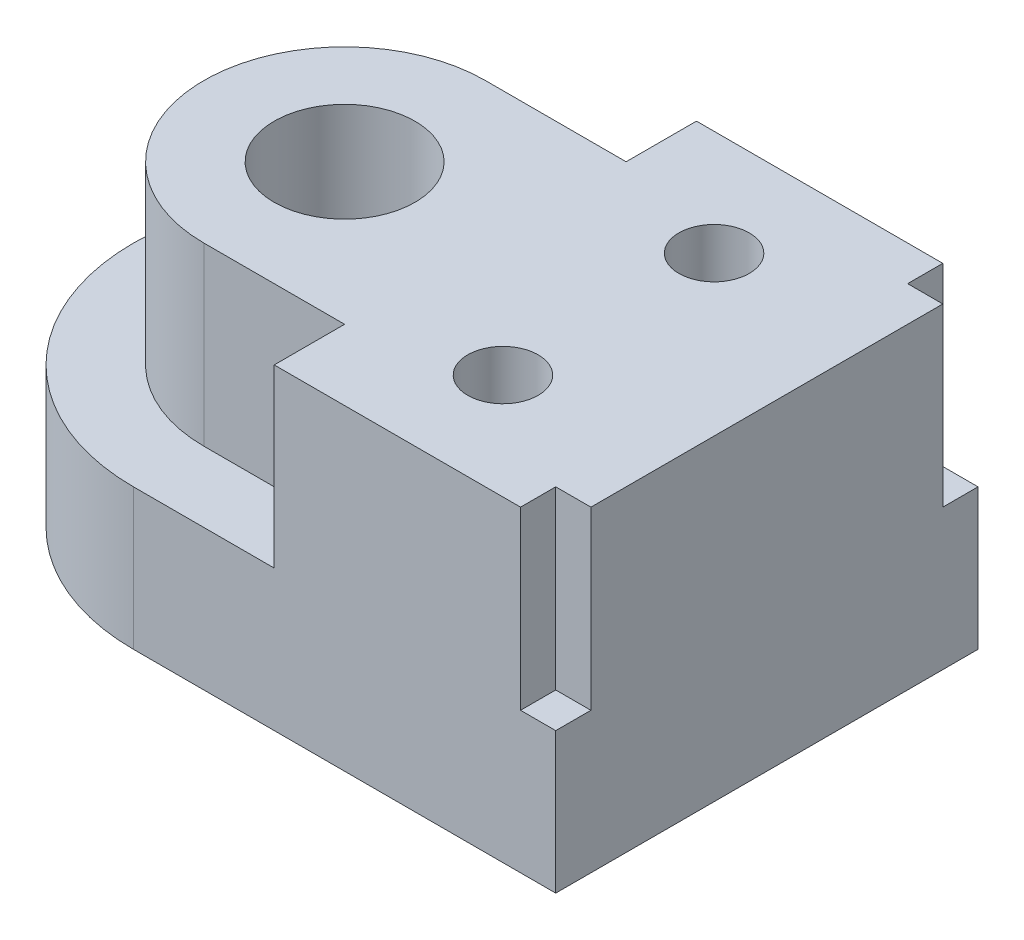
SolidWorks part; units mm, degrees
ref_plane "Front Plane" through (0, 0, 0) normal (0, 0, 1) x (1, 0, 0)
ref_plane "Top Plane" through (0, 0, 0) normal (0, 1, 0) x (1, 0, 0)
ref_plane "Right Plane" through (0, 0, 0) normal (1, 0, 0) x (0, 0, -1)
sketch "Sketch1" plane through (0, 0, 0) normal (0, 1, 0) x (1, 0, 0)
  line L0 (0, 30) -> (60, 30)
  line L1 (60, 30) -> (60, -30)
  line L2 (60, -30) -> (0, -30)
  line L3 (-20, 0) -> (60, 0) construction
  line L4 (0, 20) -> (20, 20)
  line L5 (20, 20) -> (20, 30)
  line L6 (20, -20) -> (20, -30)
  line L7 (0, -20) -> (20, -20)
  arc A0 (0, 30) -> (0, -30) centre (0, 0) ccw
  circle A1 centre (0, 0) radius 20
  dimension "D1" = 60
  dimension "D3" = 40
  dimension "D2" = 60
extrude "Boss-Extrude2" add sketch "Sketch1" along normal blind 45 contours L3 A1 | L3 A1 L7 L6 L2 L1 | A1 L3 L1 L0 L5 L4 | A1 L3 region at (38.3666, 0, -15.0356) region at (38.3666, 0, 15.0356) region at (0, 0, -8.4883) region at (0, 0, 8.4883)
extrude "Boss-Extrude3" add sketch "Sketch1<3>" along normal blind 20 contours A1 L4 L5 L0 A0 L2 L6 L7 region at (10, 0, -29.219)
sketch "Sketch1<3>" plane through (0, 0, 0) normal (0, 1, 0) x (1, 0, 0) same geometry as "Sketch1"
sketch "Sketch3" plane through (0, 45, 0) normal (0, 1, 0) x (1, 0, 0)
  line L0 (55, -30) -> (55, -25)
  line L1 (55, -25) -> (60, -25)
  line L2 (55, 30) -> (55, 25)
  line L3 (55, 25) -> (60, 25)
  line L4 (60, 25) -> (60, 30)
  line L7 (20, 20) -> (0, 20)
  line L8 (0, -20) -> (20, -20)
  line L9 (20, -20) -> (20, -30)
  line L10 (20, -30) -> (60, -30)
  line L11 (60, -30) -> (60, 30)
  line L12 (60, 30) -> (20, 30)
  line L13 (20, 30) -> (20, 20)
  line L17 (55, -30) -> (60, -30)
  line L18 (60, -30) -> (60, -25)
  line L19 (60, 30) -> (55, 30)
  arc A1 (0, 20) -> (0, -20) centre (0, 0) ccw
  point P17 (55.893, 25)
  dimension "D2" = 5
  dimension "D3" = 5
  dimension "D1" = 0
extrude "Cut-Extrude1" cut sketch "Sketch3" against normal blind 25
sketch "Sketch4" plane through (0, 45, 0) normal (0, 1, 0) x (1, 0, 0)
  line L0 (37.5, 30) -> (37.5, -30) construction
  line L1 (20, 30) -> (55, 30) construction
  line L2 (55, -30) -> (20, -30) construction
  line L3 (-20, 0) -> (60, 0) construction
  line L4 (60, 25) -> (60, -25) construction
  circle A0 centre (0, 0) radius 10
  arc A1 (0, 20) -> (0, -20) centre (0, 0) ccw construction
  circle A2 centre (37.5, 15) radius 5
  circle A3 centre (37.5, -15) radius 5
  arc A4 (0, 20) -> (0, -20) centre (0, 0) ccw construction
  point P23 (37.5, 0)
  dimension "D1" = 20
  dimension "D2" = 10
  dimension "D3" = 15
  dimension "D4" = 15
extrude "Cut-Extrude2" cut sketch "Sketch4" against normal through all
